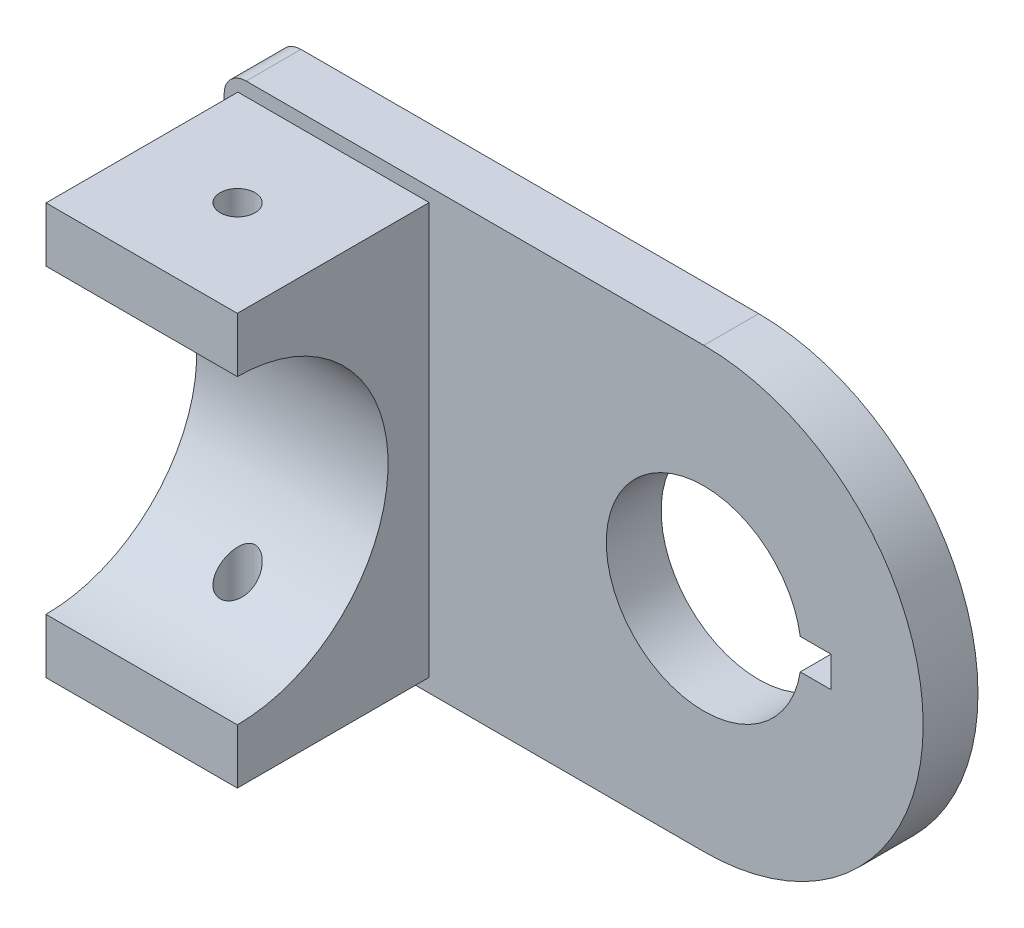
SolidWorks part; units mm, degrees
material "PET"
ref_plane "Front Plane" through (0, 0, 0) normal (0, 0, 1) x (1, 0, 0)
ref_plane "Top Plane" through (0, 0, 0) normal (0, 1, 0) x (1, 0, 0)
ref_plane "Right Plane" through (0, 0, 0) normal (1, 0, 0) x (0, 0, -1)
sketch "Sketch1" plane through (0, 0, 0) normal (0, 0, 1) x (1, 0, 0)
  line L0 (66.7248, 27.178) -> (70.2808, 27.178)
  line L1 (2.54, 0) -> (55.5625, 0)
  line L2 (0, 2.54) -> (0, 48.26)
  line L3 (2.54, 50.8) -> (55.5625, 50.8)
  line L5 (70.2808, 27.178) -> (70.2808, 23.622)
  line L6 (70.2808, 23.622) -> (66.7248, 23.622)
  line L7 (55.5625, 25.4) -> (73.7816, 25.4) construction
  arc A0 (55.5625, 0) -> (55.5625, 50.8) centre (55.5625, 25.4) ccw
  arc A1 (66.7248, 27.178) -> (66.7248, 23.622) centre (55.5625, 25.4) ccw
  arc A2 (2.54, 0) -> (0, 2.54) centre (2.54, 2.54) cw
  arc A3 (2.54, 50.8) -> (0, 48.26) centre (2.54, 48.26) ccw
  point P9 (64.6721, 25.4)
  point P14 (0, 0)
  point P17 (0, 50.8)
  dimension "D3" = 25.4
  dimension "D4" = 25.4
  dimension "D5" = 22.606
  dimension "D9" = 2.54
  dimension "D1" = 55.5625
  dimension "D2" = 50.8
  dimension "D6" = 1.778
  dimension "D7" = 1.778
  dimension "D8" = 3.556
extrude "Boss-Extrude1" add sketch "Sketch1" along normal blind 6.35
sketch "Sketch2" plane through (0, 0, 6.35) normal (0, 0, 1) x (1, 0, 0)
  line L0 (2.54, 0) -> (55.5625, 0) construction
  line L1 (1.5875, 1.5875) -> (23.749, 1.5875)
  line L2 (1.5875, 1.5875) -> (1.5875, 49.2125)
  line L3 (1.5875, 49.2125) -> (23.749, 49.2125)
  line L4 (23.749, 1.5875) -> (23.749, 49.2125)
  line L6 (0, 48.26) -> (0, 2.54) construction
  dimension "D1" = 22.1615
  dimension "D2" = 47.625
  dimension "D3" = 1.5875
  dimension "D4" = 1.5875
extrude "Boss-Extrude2" add sketch "Sketch2" along normal blind 22.225
sketch "Sketch3" plane through (1.5875, 0, 0) normal (-1, 0, 0) x (0, 0, 1)
  line L2 (28.575, 49.2125) -> (28.575, 1.5875) construction
  line L3 (28.575, 1.5875) -> (6.35, 1.5875) construction
  arc A1 (28.575, 7.9375) -> (28.575, 42.8625) centre (28.575, 25.4) cw
  dimension "D1" = 6.35
extrude "Cut-Extrude1" cut sketch "Sketch3" against normal blind 57.531 and the other way through all flip side to cut
hole_wizard "#10-32 Tapped Hole1" positions "Sketch7" profile "Sketch6" tap size "#10-32" standard "ANSI Inch" end condition up to next
sketch "Sketch7" plane through (0, 49.2125, 0) normal (0, 1, 0) x (1, 0, 0)
  line L0 (12.6682, -6.35) -> (12.6683, -28.575) construction
  line L1 (23.749, -6.35) -> (1.5875, -6.35) construction
  line L2 (23.749, -28.575) -> (1.5875, -28.575) construction
  line L4 (1.5875, -17.4625) -> (23.749, -17.4625) construction
  line L5 (1.5875, -28.575) -> (1.5875, -6.35) construction
  line L6 (23.749, -28.575) -> (23.749, -6.35) construction
  point P0 (12.6683, -17.4625)
sketch "Sketch6" plane through (12.6683, 49.2125, 17.4625) normal (1, 0, 0) x (0, 0, 1)
  line L0 (0, 0) -> (0, 10.3421)
  line L1 (0, 10.3421) -> (2.0193, 10.3421)
  line L2 (2.0193, 10.3421) -> (2.0193, 0)
  line L5 (2.0193, 0) -> (0, 0)
  line L11 (0, -6.35) -> (0, 107.95) construction
  dimension "Thru Tap Drill Dia." = 4.0386
  dimension "Thru Tap Drill Depth" = 10.3421
cosmetic thread "Hole Thread1" parameters "D2"=4.826
hole_wizard "#10-32 Tapped Hole2" positions "Sketch8" profile "Sketch9" tap size "#10-32" standard "ANSI Inch" end condition up to next
sketch "Sketch8" plane through (0, 1.5875, 0) normal (0, -1, 0) x (-1, 0, 0)
  point P22 (-12.6683, -17.4625)
sketch "Sketch9" plane through (12.6683, 1.5875, 17.4625) normal (1, 0, 0) x (0, 0, -1)
  line L0 (0, 0) -> (0, 10.3421)
  line L1 (0, 10.3421) -> (2.0193, 10.3421)
  line L2 (2.0193, 10.3421) -> (2.0193, 0)
  line L5 (2.0193, 0) -> (0, 0)
  line L11 (0, -6.35) -> (0, 107.95) construction
  dimension "Thru Tap Drill Dia." = 4.0386
  dimension "Thru Tap Drill Depth" = 10.3421
cosmetic thread "Hole Thread2" parameters "D2"=4.826
